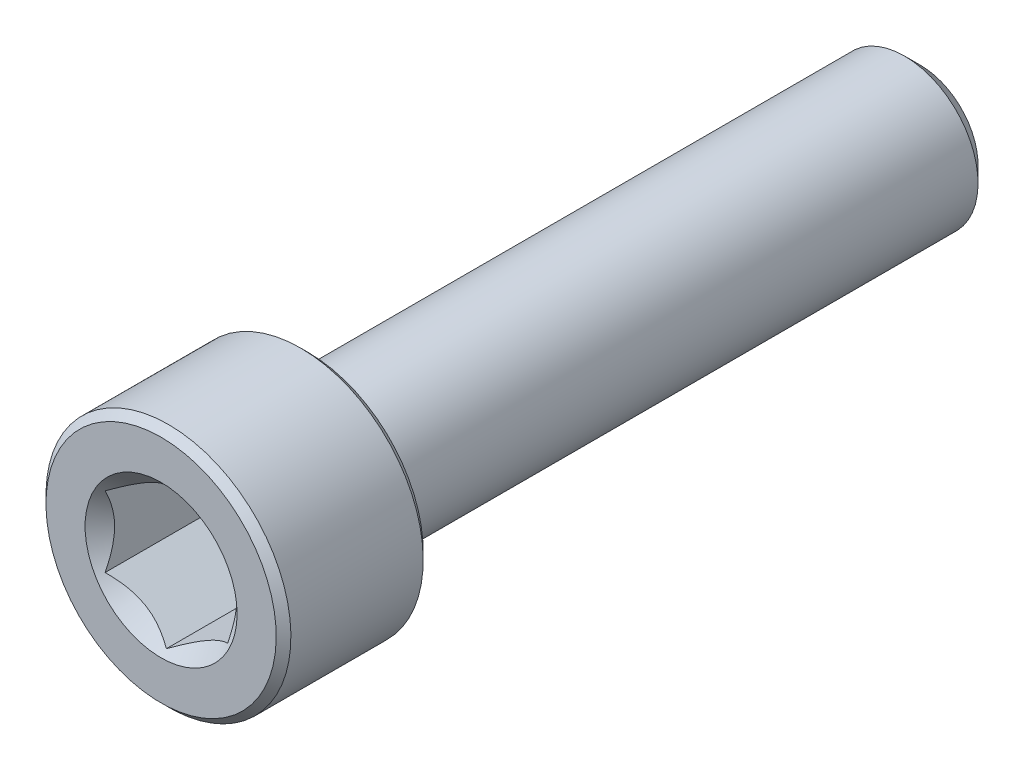
SolidWorks part; units mm, degrees
material "Alloy Steel (SS)"
ref_plane "Front Plane" through (0, 0, 0) normal (0, 0, 1) x (1, 0, 0)
ref_plane "Top Plane" through (0, 0, 0) normal (0, 1, 0) x (1, 0, 0)
ref_plane "Right Plane" through (0, 0, 0) normal (1, 0, 0) x (0, 0, -1)
sketch "Sketch1" plane through (0, 0, 0) normal (1, 0, 0) x (0, 0, -1)
  line L0 (-15.5, 0) -> (15.5, 0) construction
  line L1 (15.5, 0) -> (15.5, 2.3505) construction
  line L2 (15.5, 2.3505) -> (14.8505, 3) construction
  line L3 (14.8505, 3) -> (14.75, 3) construction
  line L4 (14.75, 3) -> (-9.5, 3) construction
  line L5 (-9.5, 3) -> (-9.5, 5) construction
  line L6 (-9.5, 5) -> (-15.5, 5) construction
  line L7 (-15.5, 5) -> (-15.5, 0) construction
  line L8 (15.5, 2.3505) -> (15.5, 3) construction
  line L9 (15.4375, 3.1083) -> (15.9375, 2.2422) construction
  line L10 (15.9375, 2.2422) -> (16.4375, 3.1083) construction
  line L11 (16.4375, 3.1083) -> (15.4375, 3.1083) construction
  line L12 (15.9375, 3.1083) -> (15.9375, 3) construction
  line L13 (15.9375, 2.2422) -> (15.9375, 2.3505) construction
  line L14 (15.875, 2.3505) -> (16, 2.3505) construction
  line L15 (15.5, 3) -> (16.375, 3) construction
  line L16 (15.4687, 3.0541) -> (16.4063, 3.0541) construction
  line L17 (15.5, 0) -> (15.5, -3) construction
  line L18 (-9.8, 5) -> (-9.5, 4.7) construction
  line L19 (-15.2, 5) -> (-15.5, 4.7) construction
  line L20 (-9.5, 3) -> (-9.5, 0) construction
  line L21 (-9.5, 1.5) -> (-1.1667, 1.5) construction
  line L22 (-1.1667, 1.5) -> (7.1667, 1.5) construction
  line L23 (7.1667, 1.5) -> (15.5, 1.5) construction
  line L24 (-1.1667, 1.5) -> (-1.1667, 3) construction
  line L25 (-1.1667, 3) -> (-1.1667, 5) construction
  line L26 (7.1667, 1.5) -> (7.1667, 5) construction
  point P0 (-15.5, 2.5)
  point P3 (13, 3)
  point P4 (0, 0)
  point P18 (7.1667, 3)
  point P22 (15.9375, 2.3505)
  point P24 (14.75, 3)
  point P25 (15.9375, 3)
  point P28 (15.9375, 3.0541)
  point P29 (13, -3)
  point P30 (-1.1667, 3)
  point P31 (-12.5, 5)
  point P37 (-10.55, 5)
  point P38 (-15.05, 5)
  point P45 (-1.1667, 1.5)
  point P46 (7.1667, 1.5)
  dimension "D2" = 0.125
  dimension "D7" = 0.3
  dimension "D8" = 0.3
  dimension "D9" = 0.3
  dimension "D10" = 0.15
  dimension "D11" = 0.75
  dimension "Drive Size" = 5
  dimension "Head Diameter" = 10
  dimension "Head Height" = 6
  dimension "Thread Pitch" = 1
  dimension "Thread Dia" = 6
  dimension "Length" = 25
  dimension "D12" = 0.75
  dimension "D4" = 2.5
  dimension "D3" = 45
sketch "Sketch2" plane through (0, 0, 0) normal (1, 0, 0) x (0, 0, -1)
  line L0 (-15.5, 0) -> (-15.5, 4.7)
  line L1 (-15.2, 5) -> (-9.8, 5)
  line L2 (-9.5, 4.7) -> (-9.5, 3.3)
  line L4 (14.8505, 3) -> (15.5, 2.3505)
  line L5 (15.5, 2.3505) -> (15.5, 0)
  line L6 (-9.5, 5) -> (-15.5, 5) construction
  line L7 (15.5, 0) -> (-15.5, 0)
  line L8 (-15.2, 5) -> (-15.5, 4.7) construction
  line L10 (-15.2, 5) -> (-15.5, 4.7)
  line L14 (-9.8, 5) -> (-9.5, 4.7) construction
  line L16 (-9.8, 5) -> (-9.5, 4.7)
  line L17 (-9.5, 3) -> (-9.5, 5) construction
  line L19 (-9.2, 3) -> (14.8505, 3)
  line L20 (14.75, 3) -> (-9.5, 3) construction
  arc A1 (-9.5, 3.3) -> (-9.2, 3) centre (-9.2, 3.3) ccw
  dimension "D3" = 0.3
revolve "Revolve1" add sketch "Sketch2" angle 360 about L7
sketch "Sketch3" plane through (0, 0, 15.5) normal (0, 0, 1) x (1, 0, 0)
  line L1 (2.5, -1.4434) -> (2.5, 1.4434)
  line L2 (2.5, 1.4434) -> (0, 2.8868)
  line L3 (0, 2.8868) -> (-2.5, 1.4434)
  line L4 (-2.5, 1.4434) -> (-2.5, -1.4434)
  line L5 (-2.5, -1.4434) -> (0, -2.8868)
  line L6 (0, -2.8868) -> (2.5, -1.4434)
  circle A0 centre (0, 0) radius 2.5 construction
  circle A1 centre (0, 0) radius 5 construction
  circle A2 centre (0, 0) radius 5 construction
  circle A3 centre (0, 0) radius 2.8868 construction
  point P13 (0, 0)
  dimension "D1" = 5.7735
extrude "Cut-Extrude1" cut sketch "Sketch3" against normal offset from surface (5 mm away) 1 up to face at (0, 4.7, 9.5)
sketch "Sketch4" plane through (0, 0, 15.5) normal (0, 0, 1) x (1, 0, 0)
  circle A0 centre (0, 0) radius 3.1033
  dimension "D1" = 6.2065
extrude "Cut-Extrude2" cut sketch "Sketch4" against normal up to vertex (3 mm away) draft 45 up to point (0, 5, 12.5)
sketch "Sketch11" plane through (0, 0, 0) normal (1, 0, 0) x (0, 0, -1)
  line L0 (-15.5, 0) -> (15.5, 0) construction
  line L1 (-15.5, 0) -> (15.5, 0) construction
  line L2 (-4.8125, 0) -> (-4.8125, 3) construction
  line L3 (14.75, 3) -> (-9.5, 3) construction
  line L4 (10.8125, 0) -> (10.8125, 3) construction
  line L6 (15.5, 2.3505) -> (15.5, 3) construction
  point P2 (-4.8125, 0)
  point P3 (10.8125, 0)
  dimension "D1" = 4.6875
  dimension "D2" = 4.6875
sketch "Sketch6" [suppressed] plane through (0, 0, -15.5) normal (0, 0, -1) x (-1, 0, 0)
  circle A0 centre (0, 0) radius 3
curve "Helix/Spiral1" [suppressed] pitch 1 height 26 turns 26
sketch "Sketch10" [suppressed] plane through (0, 0, 0) normal (1, 0, 0) x (0, 0, -1)
  line L0 (-9.2, -5) -> (-9.2, 5)
  line L5 (-15.5, 0) -> (15.5, 0) construction
  line L6 (-9.2, 3) -> (-9.2, -3) construction
  point P3 (-9.2, 0)
split "Split1" [suppressed] bodies to split 106
sketch "Sketch7" [suppressed] plane through (0, 0, 0) normal (1, 0, 0) x (0, 0, -1)
  line L0 (15.4687, 3.0541) -> (16.4063, 3.0541)
  line L1 (16.4063, 3.0541) -> (16, 2.3505)
  line L2 (16, 2.3505) -> (15.875, 2.3505)
  line L3 (15.875, 2.3505) -> (15.4687, 3.0541)
sweep "Cut-Sweep1" [suppressed] cut profiles "Sketch7" path "Helix/Spiral1"
sketch "Sketch8" [suppressed] plane through (0, 0, 0) normal (1, 0, 0) x (0, 0, -1)
  line L0 (-9.5, 0) -> (-9.5, 3)
  line L1 (-9.2, -3) -> (-9.2, 3) construction
  line L2 (-9.5, 3) -> (-9.2, 3)
  line L4 (-9.2, 3) -> (-7.4679, 0)
  line L5 (-7.4679, 0) -> (-9.5, 0)
  line L6 (14.75, 3) -> (-9.5, 3) construction
  line L7 (-15.5, 0) -> (15.5, 0) construction
  dimension "D1" = 60
revolve "Revolve2" [suppressed] add sketch "Sketch8" angle 360 about L5
equation "\"D2@Sketch1\" = \"Thread Pitch@Sketch1\" / 8"
equation "\"D4@Helix/Spiral1\" = \"Thread Pitch@Sketch1\""
equation "\"D7@Sketch1\" = \"Head Height@Sketch1\" * .05"
equation "\"D8@Sketch1\"=\"D7@Sketch1\""
equation "\"D9@Sketch1\"=\"D7@Sketch1\""
equation "\"D10@Sketch1\"=\"D7@Sketch1\"/2"
equation "\"D11@Sketch1\"=\"D10@Sketch1\"*5"
equation "\"D4@Sketch1\"=\"Thread Pitch@Sketch1\"*2.5"
equation "\"D12@Sketch1\"=\"Thread Pitch@Sketch1\"*.75"
equation "\"D3@Helix/Spiral1\"=\"Length@Sketch1\"+\"Thread Pitch@Sketch1\""
equation "\"D3@Sketch2\"=\"Thread Dia@Sketch1\"*0.05"
equation "\"D1@Sketch11\"=\"Length@Sketch1\"*0.1875"
equation "\"D2@Sketch11\"=\"D1@Sketch11\""
equation "\"D1@Sketch4\"=\"D1@Sketch3\"*1.075"
